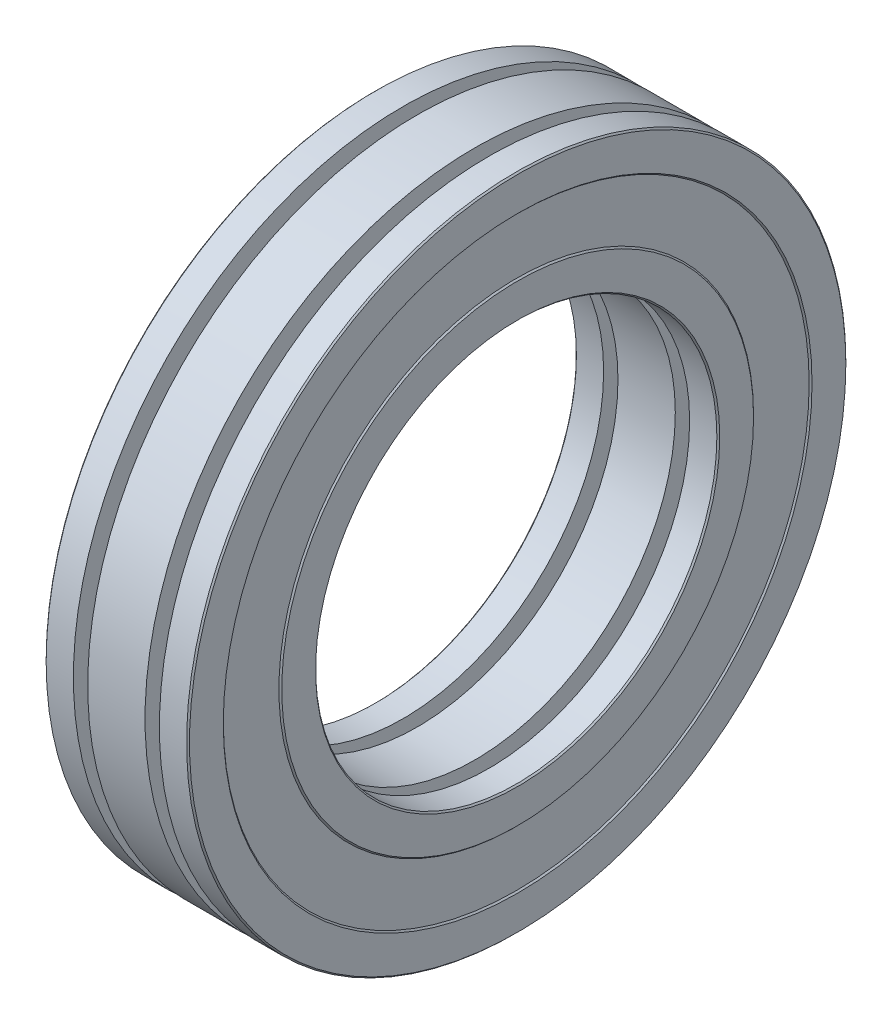
SolidWorks part; units mm, degrees
ref_plane "Piano frontale" through (0, 0, 0) normal (0, 0, 1) x (1, 0, 0)
ref_plane "Piano superiore" through (0, 0, 0) normal (0, 1, 0) x (1, 0, 0)
ref_plane "Piano destro" through (0, 0, 0) normal (1, 0, 0) x (0, 0, -1)
sketch "Schizzo1" plane through (0, 0, 0) normal (0, 0, 1) x (1, 0, 0)
  line L0 (0.9352, 7) -> (1.9352, 7)
  line L1 (5.9352, 7) -> (5.9352, 8.2802)
  line L2 (5.9352, 8.2802) -> (5.8852, 8.2802)
  line L3 (5.8852, 8.2802) -> (5.8852, 10.2198)
  line L4 (5.8852, 10.2198) -> (5.9352, 10.2198)
  line L5 (5.9352, 10.2198) -> (5.9352, 11.5)
  line L6 (5.9352, 11.5) -> (4.9352, 11.5)
  line L7 (0.9352, 11.5) -> (0.9352, 10.2198)
  line L8 (0.9352, 10.2198) -> (0.9852, 10.2198)
  line L9 (0.9852, 10.2198) -> (0.9852, 8.2802)
  line L10 (0.9852, 8.2802) -> (0.9352, 8.2802)
  line L11 (0.9352, 8.2802) -> (0.9352, 7)
  line L12 (0, 0) -> (-7.4977, 0) construction
  line L13 (1.9352, 11.5) -> (1.9352, 10.7)
  line L14 (1.9352, 10.7) -> (2.4352, 10.7)
  line L15 (2.4352, 10.7) -> (2.4352, 11.5)
  line L16 (4.4352, 11.5) -> (4.4352, 10.7)
  line L17 (4.4352, 10.7) -> (4.9352, 10.7)
  line L18 (4.9352, 10.7) -> (4.9352, 11.5)
  line L19 (1.9352, 7) -> (1.9352, 7.8)
  line L20 (1.9352, 7.8) -> (2.4352, 7.8)
  line L21 (2.4352, 7.8) -> (2.4352, 7)
  line L22 (4.4352, 7) -> (4.4352, 7.8)
  line L23 (4.4352, 7.8) -> (4.9352, 7.8)
  line L24 (4.9352, 7.8) -> (4.9352, 7)
  line L25 (1.9352, 11.5) -> (0.9352, 11.5)
  line L26 (4.4352, 11.5) -> (2.4352, 11.5)
  line L27 (2.4352, 7) -> (4.4352, 7)
  line L28 (4.9352, 7) -> (5.9352, 7)
  point P31 (0.9352, 10.8599)
  dimension "D1" = 4.5
  dimension "D2" = 0.05
  dimension "D3" = 7
  dimension "D4" = 0.8
  dimension "D5" = 0.8
  dimension "D6" = 0.5
  dimension "D7" = 0.5
  dimension "D8" = 1
  dimension "D9" = 1
  dimension "D10" = 5
revolve "Rivoluzione1" add sketch "Schizzo1" angle 360 about L12
chamfer "Smusso1" distance 0.05 angle 45 8 edges at (0.9352, 0, -8.2802) (0.9352, 0, -7) (0.9352, 0, -11.5) (0.9352, 0, -10.2198) (5.9352, 0, -7) (5.9352, 0, -8.2802) (5.9352, 0, -10.2198) (5.9352, 0, -11.5)
